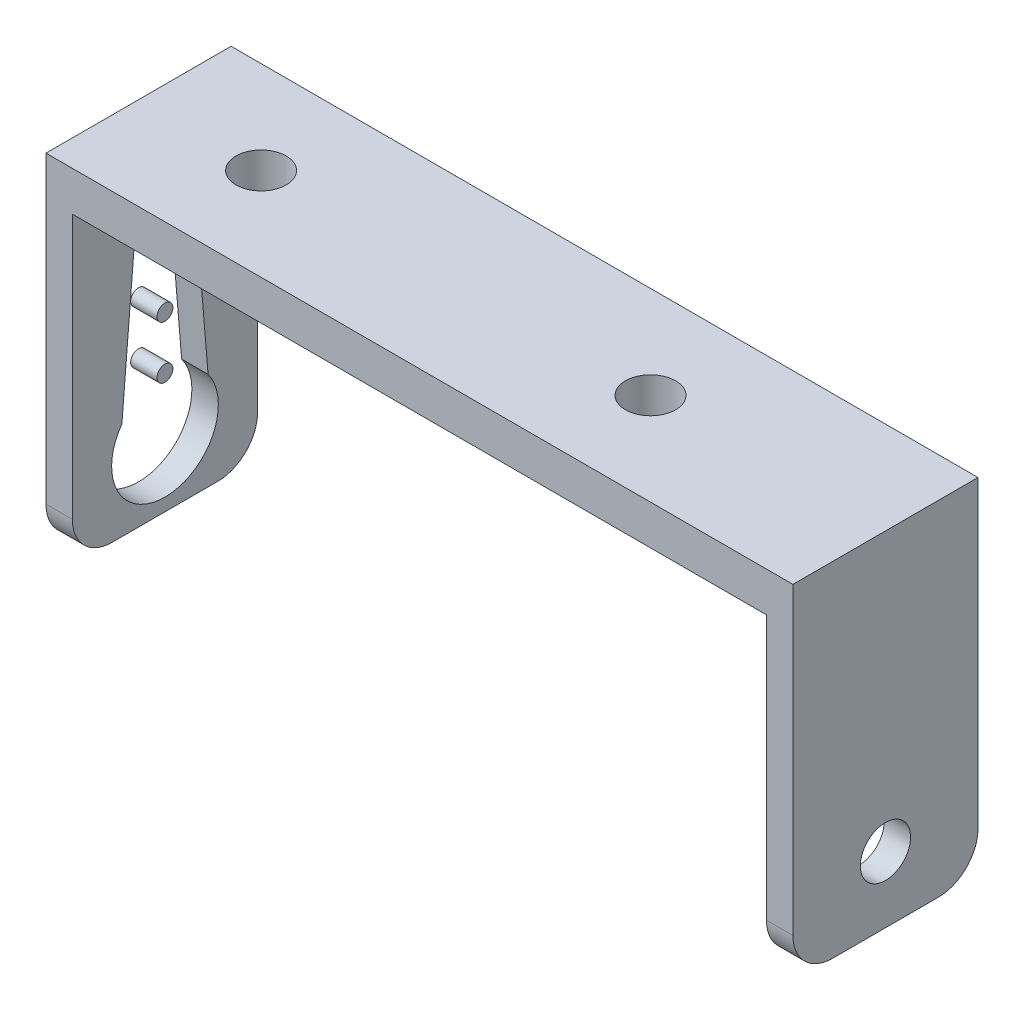
SolidWorks part; units mm, degrees
ref_plane "前视基准面" through (0, 0, 0) normal (0, 0, 1) x (1, 0, 0)
ref_plane "上视基准面" through (0, 0, 0) normal (0, 1, 0) x (1, 0, 0)
ref_plane "右视基准面" through (0, 0, 0) normal (1, 0, 0) x (0, 0, -1)
sketch "草图1" plane through (0, 0, 0) normal (0, 0, 1) x (1, 0, 0)
  line L0 (-28.25, 0) -> (-28.25, 19)
  line L2 (28.25, 19) -> (28.25, 0)
  line L3 (28.25, 0) -> (26.25, 0)
  line L4 (26.25, 0) -> (26.25, 16)
  line L6 (-26.25, 16) -> (-26.25, 0)
  line L7 (-26.25, 0) -> (-28.25, 0)
  line L8 (-61.4321, 26.241) -> (-59.0057, 26.241)
  line L9 (0, 0) -> (0, 21.894) construction
  line L10 (26.25, 23) -> (-26.25, 23)
  line L11 (28.25, 26) -> (-28.25, 26)
  line L13 (28.25, 26) -> (28.25, 23)
  line L14 (-28.25, 23) -> (-28.25, 26)
  line L15 (28.25, 23) -> (28.25, 19)
  line L16 (-26.25, 16) -> (-26.25, 23)
  line L17 (26.25, 16) -> (26.25, 23)
  line L19 (-28.25, 23) -> (-28.25, 19)
  dimension "D1" = 56.5
  dimension "D2" = 19
  dimension "D4" = 2
  dimension "D5" = 2
  dimension "D6" = 19
extrude "凸台-拉伸1" add sketch "草图1" along normal blind 14 contours L9 L0 L7 L6 | L9 L4 L3 L2 region at (-27.628, 9.5, 0)
sketch "草图2" plane through (28.25, 0, 0) normal (1, 0, 0) x (0, 0, -1)
  line L0 (-7, 0) -> (-7, 19) construction
  line L1 (-14, 0) -> (0, 0) construction
  circle A0 centre (-7, 5) radius 1.9
  dimension "D2" = 3.8
  dimension "D1" = 5
extrude "切除-拉伸1" cut sketch "草图2" against normal up to surface (2 mm away) up to face at (26.25, 11.5, 7)
sketch "草图3" plane through (0, 19, 0) normal (0, 1, 0) x (1, 0, 0)
  line L0 (-28.25, -7) -> (28.25, -7) construction
  line L3 (0, 0) -> (0, -14) construction
  line L6 (-4.25, 0) -> (-4.25, -14) construction
  circle A0 centre (-18.98, -7) radius 1.9
  circle A1 centre (10.48, -7) radius 1.9
  dimension "D2" = 3.8
  dimension "D1" = 29.46
  dimension "D3" = 4.25
extrude "切除-拉伸2" cut sketch "草图3" along normal blind 14
fillet "圆角1" radius 3 4 edges at (27.25, 0, 14) (-27.25, 0, 14) (-27.25, 0, 0) (27.25, 0, 0)
sketch "草图5" plane through (-28.25, 0, 0) normal (-1, 0, 0) x (0, 0, 1)
  line L0 (7, 5) -> (7, 20.3188) construction
  line L1 (7, 5) -> (7, 40.57) construction
  line L2 (7, 40.57) -> (9.9556, 5) construction
  line L3 (7, 40.57) -> (4.0444, 5) construction
  line L6 (3.7402, 7.3781) -> (4.7278, 19.2633)
  line L7 (9.2722, 19.2633) -> (10.2598, 7.3781)
  line L8 (8.7739, 19.2219) -> (9.7735, 7.1918)
  line L9 (4.2265, 7.1918) -> (5.2261, 19.2219)
  circle A0 centre (7, 5) radius 1.9 construction
  circle A1 centre (7, 5) radius 1.9 construction
  circle A2 centre (7, 9.085) radius 0.6
  circle A3 centre (7, 13.085) radius 0.6
  arc A5 (4.2265, 7.1918) -> (9.7735, 7.1918) centre (7, 5) ccw
  arc A7 (8.7739, 19.2219) -> (5.2261, 19.2219) centre (7, 19.0745) ccw
  arc A8 (9.2722, 19.2633) -> (4.7278, 19.2633) centre (7, 19.0745) ccw
  arc A9 (3.7402, 7.3781) -> (10.2598, 7.3781) centre (7, 5) ccw
  dimension "D1" = 1.2
  dimension "D4" = 0.5
  dimension "D2" = 4.085
  dimension "D3" = 8.085
  dimension "D5" = 35.57
  dimension "D6" = 9.5
extrude "切除-拉伸3" cut sketch "草图5" against normal blind 10 contours L6 A9 L7 A8 A3 A2 | A2 | A3 | L6 A8 L7 A9 | A3 region at (-28.25, 13.3025, 4.4526) region at (-28.25, 9.085, 7) region at (-28.25, 13.085, 7)
